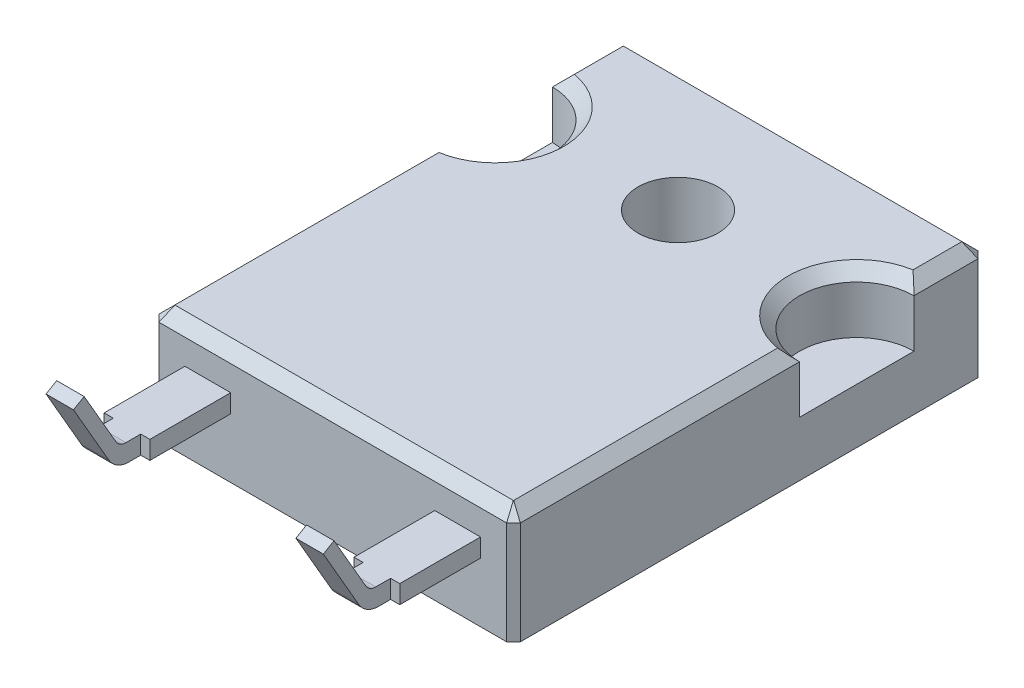
SolidWorks part; units mm, degrees
ref_plane "Спереди" through (0, 0, 0) normal (0, 0, 1) x (1, 0, 0)
ref_plane "Сверху" through (0, 0, 0) normal (0, 1, 0) x (1, 0, 0)
ref_plane "Справа" through (0, 0, 0) normal (1, 0, 0) x (0, 0, -1)
sketch "Эскиз1" plane through (0, 0, 0) normal (0, 1, 0) x (1, 0, 0)
  line L0 (0, 4.79) -> (0, -49995.21) construction
  line L1 (7.9, -10.3) -> (-7.9, -10.3)
  line L2 (7.9, -10.3) -> (7.9, 10.3)
  line L3 (7.9, 10.3) -> (-7.9, 10.3)
  line L4 (-7.9, -10.3) -> (-7.9, 10.3)
  line L5 (7.9, -10.3) -> (-7.9, 10.3) construction
  line L6 (7.9, 10.3) -> (-7.9, -10.3) construction
  line L7 (-5.46, 4.79) -> (-5.46, -49995.21) construction
  line L8 (5.46, 4.79) -> (5.46, -49995.21) construction
  line L9 (-6.46, 4.79) -> (-6.46, -49995.21) construction
  line L10 (-4.46, 4.79) -> (-4.46, -49995.21) construction
  line L11 (6.46, -10.3) -> (6.46, -13.83)
  line L12 (-6.46, -10.3) -> (-4.46, -10.3)
  line L13 (-6.46, -10.3) -> (-6.46, -13.83)
  line L14 (-6.46, -13.83) -> (-4.46, -13.83)
  line L15 (-4.46, -10.3) -> (-4.46, -13.83)
  line L16 (-6.46, -10.3) -> (-4.46, -13.83) construction
  line L17 (-6.46, -13.83) -> (-4.46, -10.3) construction
  line L18 (6.46, -13.83) -> (4.46, -13.83)
  line L19 (4.46, -10.3) -> (4.46, -13.83)
  line L20 (-6.06, 4.79) -> (-6.06, -49995.21) construction
  line L21 (-4.86, 4.79) -> (-4.86, -49995.21) construction
  line L22 (4.86, -13.83) -> (4.86, -14.93)
  line L23 (-6.06, -13.83) -> (-4.86, -13.83)
  line L24 (-6.06, -13.83) -> (-6.06, -14.93)
  line L25 (-6.06, -14.93) -> (-4.86, -14.93)
  line L26 (-4.86, -13.83) -> (-4.86, -14.93)
  line L27 (-6.06, -13.83) -> (-4.86, -14.93) construction
  line L28 (-6.06, -14.93) -> (-4.86, -13.83) construction
  line L29 (6.06, -14.93) -> (4.86, -14.93)
  line L30 (6.06, -13.83) -> (6.06, -14.93)
  line L31 (-6.06, -14.13) -> (-4.86, -14.13)
  line L32 (6.06, -14.13) -> (4.86, -14.13)
  circle A0 centre (0, 4.79) radius 1.75
  arc A1 (-7.9, 2.2) -> (-7.9, 7.2) centre (-7.9, 4.7) ccw
  arc A2 (7.9, 2.2) -> (7.9, 7.2) centre (7.9, 4.7) cw
  point P0 (0, 0)
  point P25 (-5.46, -12.065)
  point P38 (-5.46, -14.38)
  dimension "D3" = 3.5
  dimension "D6" = 5.6
  dimension "D7" = 5
  dimension "D1" = 15.8
  dimension "D2" = 20.6
  dimension "D4" = 7.9
  dimension "D5" = 5.51
  dimension "D8" = 5.46
  dimension "D9" = 5.46
  dimension "D12" = 3.53
  dimension "D15" = 1.1
  dimension "D16" = 0.8
  dimension "D10" = 1
  dimension "D11" = 1
  dimension "D13" = 0.6
  dimension "D14" = 0.6
extrude "Бобышка-Вытянуть1" add sketch "Эскиз1" along normal blind 2.6 contours L2 A2 L3 L4 A1 L1 A0 region at (0, 0, 0.4671)
extrude "Бобышка-Вытянуть2" add sketch "Эскиз1<3>" against normal blind 2.4 contours L2 A2 L3 L4 A1 L1 A0 | A2 L2 | L4 A1 region at (0, 0, 0.4671) region at (6.839, 0, -4.7) region at (-6.839, 0, -4.7)
sketch "Эскиз1<3>" plane through (0, 0, 0) normal (0, 1, 0) x (1, 0, 0) same geometry as "Эскиз1"
extrude "Бобышка-Вытянуть3" add sketch "Эскиз1<4>" along normal blind 0.8 from offset 0.2 separate body contours L15 L1 L13 L14 | L24 L31 L26 L14 | L31 L24 L25 L26 | L1 L19 L18 L11 | L32 L30 L18 L22 | L30 L32 L22 L29 region at (5.46, 0, 12.065) region at (-5.46, 0, 12.065) region at (5.46, 0, 13.98) region at (5.46, 0, 14.53) region at (-5.46, 0, 13.98) region at (-5.46, 0, 14.53)
sketch "Эскиз1<4>" plane through (0, 0, 0) normal (0, 1, 0) x (1, 0, 0) same geometry as "Эскиз1"
chamfer "Фаска1" distance 0.3 angle 45 4 edges at (-7.9, 0.1, 10.3) (-7.9, 0.1, -10.3) (7.9, 0.1, -10.3) (7.9, 0.1, 10.3)
chamfer "Фаска2" distance 0.5 angle 45 12 edges at (-5.4, 2.6, -4.7) (-7.9, 2.6, -8.6) (-7.75, 2.6, -10.15) (0, 2.6, -10.3) (7.75, 2.6, -10.15) (7.9, 2.6, -8.6) (5.4, 2.6, -4.7) (7.9, 2.6, 3.9) (7.75, 2.6, 10.15) (0, 2.6, 10.3) (-7.75, 2.6, 10.15) (-7.9, 2.6, 3.9)
sketch "Эскиз2" plane through (0, -2.4, 0) normal (0, -1, 0) x (1, 0, 0)
  line L0 (-6.9, -9.3) -> (6.9, -9.3)
  line L1 (6.9, -9.3) -> (6.9, -9.3)
  line L2 (6.9, -9.3) -> (6.9, 9.3)
  line L3 (6.9, 9.3) -> (6.9, 9.3)
  line L4 (6.9, 9.3) -> (-6.9, 9.3)
  line L5 (-6.9, 9.3) -> (-6.9, 9.3)
  line L6 (-6.9, 9.3) -> (-6.9, -9.3)
  line L7 (-6.9, -9.3) -> (-6.9, -9.3)
  line L8 (7.6, 10.3) -> (-7.6, 10.3)
  line L9 (-7.6, 10.3) -> (-7.9, 10)
  line L10 (-7.9, 10) -> (-7.9, -10)
  line L11 (-7.9, -10) -> (-7.6, -10.3)
  line L12 (-7.6, -10.3) -> (7.6, -10.3)
  line L13 (7.6, -10.3) -> (7.9, -10)
  line L14 (7.9, -10) -> (7.9, 10)
  line L15 (7.9, 10) -> (7.6, 10.3)
  line L16 (7.6, 10.3) -> (-7.6, 10.3)
  line L17 (-7.6, 10.3) -> (-7.9, 10)
  line L18 (-7.9, 10) -> (-7.9, -10)
  line L19 (-7.9, -10) -> (-7.6, -10.3)
  line L20 (-7.6, -10.3) -> (7.6, -10.3)
  line L21 (7.6, -10.3) -> (7.9, -10)
  line L22 (7.9, -10) -> (7.9, 10)
  line L23 (7.9, 10) -> (7.6, 10.3)
  circle A0 centre (0, -4.79) radius 1.75 construction
  circle A1 centre (0, -4.79) radius 1.75
  circle M9 centre (0, -4.79) radius 1.75
  dimension "D1" = 0
  dimension "D2" = 1
extrude "Вырез-Вытянуть1" cut sketch "Эскиз2" against normal blind 1.5 contours L4 L6 L0 L2 M9 region at (0, -2.4, 0.1865)
ref_plane "Плоскость1" through (0, 6.6149, 3.8191) normal (0, -0.866, -0.5) x (1, 0, 0)
sketch "Эскиз3" plane through (0, 6.6149, 3.8191) normal (0, -0.866, -0.5) x (1, 0, 0)
  line L0 (-6.06, 12.8298) -> (-4.86, 12.8298) construction
  line L1 (-6.06, 12.8298) -> (-4.86, 12.8298)
  line L2 (-4.86, 11.8771) -> (-4.86, 12.8298) construction
  line L3 (-6.06, 12.8298) -> (-4.86, 12.8298)
  line L4 (-6.06, 12.8298) -> (-6.06, 12.2898)
  line L5 (-6.06, 12.2898) -> (-4.86, 12.2898)
  line L6 (-4.86, 12.8298) -> (-4.86, 12.2898)
  line L7 (-6.06, 12.8298) -> (-4.86, 12.2898) construction
  line L8 (-6.06, 12.2898) -> (-4.86, 12.8298) construction
  line L9 (6.06, 12.8298) -> (6.06, 12.2898)
  line L10 (4.86, 12.2898) -> (6.06, 12.2898)
  line L11 (4.86, 12.8298) -> (6.06, 12.8298)
  line L12 (4.86, 12.8298) -> (4.86, 12.2898)
  point P4 (-5.46, 12.5598)
  point P7 (6.06, 12.8298)
  dimension "D1" = 0.54
  dimension "D2" = 2
extrude "Бобышка-Вытянуть6" add sketch "Эскиз3" against normal blind 3.68 contours L6 L1 L4 L5 | L11 L12 L10 L9 region at (-5.46, 0.335, 14.6962) region at (5.46, 0.335, 14.6962)
fillet "Скругление1" radius 1 1 edges at (-5.46, 0.2, 14.93)
fillet "Скругление2" radius 1 1 edges at (5.46, 0.2, 14.93)
fillet "Скругление3" radius 0.5 1 edges at (5.46, 1, 14.7683)
fillet "Скругление4" radius 0.5 1 edges at (-5.46, 1, 14.7683)
ref_plane "Плоскость2" through (0, -6.4149, 11.1109) normal (0, -0.5, 0.866) x (1, 0, 0)
